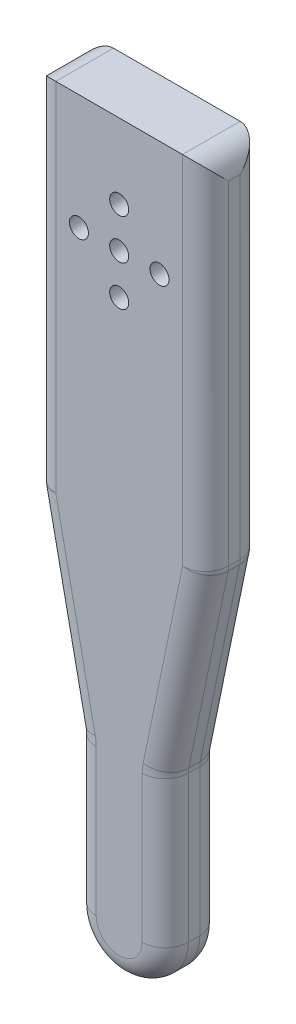
SolidWorks part; units mm, degrees
ref_plane "Front Plane" through (0, 0, 0) normal (0, 0, 1) x (1, 0, 0)
ref_plane "Top Plane" through (0, 0, 0) normal (0, 1, 0) x (1, 0, 0)
ref_plane "Right Plane" through (0, 0, 0) normal (1, 0, 0) x (0, 0, -1)
sketch "Sketch2" plane through (0, 0, 0) normal (0, 0, 1) x (1, 0, 0)
  line L1 (-29.8024, 62.3024) -> (0.1976, 62.3024)
  line L2 (-29.8024, 62.3024) -> (-29.8024, -67.6976)
  line L3 (-29.8024, -67.6976) -> (0.1976, -67.6976)
  line L4 (0.1976, 62.3024) -> (0.1976, -67.6976)
  dimension "D1" = 130
extrude "Boss-Extrude1" add sketch "Sketch2" along normal blind 10
sketch "Sketch3" plane through (0, 0, 10) normal (0, 0, 1) x (1, 0, 0)
  line L0 (-14.8024, 62.3024) -> (-14.8024, 42.3024) construction
  line L1 (0.1976, 62.3024) -> (-29.8024, 62.3024) construction
  line L4 (-29.8024, -67.6976) -> (-21.8024, -67.6976)
  line L5 (-29.8024, -67.6976) -> (-29.8024, 0)
  line L6 (-29.8024, 0) -> (-21.8024, 0)
  line L7 (-21.8024, -67.6976) -> (-21.8024, 0)
  line L9 (0, 0) -> (-7.8024, 0)
  line L10 (0, 0) -> (0, -67.6976)
  line L11 (0, -67.6976) -> (-7.8024, -67.6976)
  line L12 (-7.8024, 0) -> (-7.8024, -67.6976)
  line L13 (-29.8024, -67.6976) -> (0.1976, -67.6976) construction
  circle A0 centre (-14.8024, 42.3024) radius 7 construction
  circle A1 centre (-21.8024, 42.3024) radius 1.65
  circle A2 centre (-14.8024, 49.3024) radius 1.65
  circle A3 centre (-7.8024, 42.3024) radius 1.65
  circle A4 centre (-14.8024, 35.3024) radius 1.65
  circle A5 centre (-14.8024, 42.3024) radius 1.65
  point P5 (-21.8024, 42.3024)
  point P7 (-14.8024, 49.3024)
  point P9 (-7.8024, 42.3024)
  point P11 (-14.8024, 35.3024)
  point P13 (0, 0)
sketch "Sketch6" plane through (0, 0, 10) normal (0, 0, 1) x (1, 0, 0)
  line L1 (-29.8024, -67.6976) -> (-22.8024, -67.6976)
  line L2 (-29.8024, -67.6976) -> (-29.8024, 0)
  line L4 (-22.8024, -67.6976) -> (-22.8024, -33.8488)
  line L11 (0.1976, -67.6976) -> (-6.8024, -67.6976)
  line L12 (0.1976, -67.6976) -> (0.1976, 0)
  line L14 (-6.8024, -67.6976) -> (-6.8024, -33.8488)
  line L15 (-29.8024, 0) -> (-22.8024, -33.8488)
  line L16 (-6.8024, -33.8488) -> (0.1976, 0)
  dimension "D1" = 7
extrude "Cut-Extrude3" cut sketch "Sketch6" against normal through all contours L14 L16 L12 L11 | L4 L15 L2 L1
fillet "Fillet3" 2 edges at (-22.8024, -67.6976, 5) (-6.8024, -67.6976, 5) type full round first side face at (-22.8024, -50.7732, 5) second side face at (-6.8024, -50.7732, 5) middle face at (-14.8024, -67.6976, 5)
fillet "Fillet4" radius 4 20 edges at (-14.8024, -67.6976, 0) (-14.8024, -67.6976, 10) (-6.8024, -46.7732, 0) (-6.8024, -46.7732, 10) (-22.8024, -46.7732, 0) (-22.8024, -46.7732, 10) (0.1976, 31.1512, 10) (0.1976, 62.3024, 5) (0.1976, 31.1512, 0) (0.1976, 0, 5) (-3.3024, -16.9244, 0) (-6.8024, -33.8488, 5) (-3.3024, -16.9244, 10) (-22.8024, -33.8488, 5) (-26.3024, -16.9244, 0) (-26.3024, -16.9244, 10) (-29.8024, 31.1512, 0) (-29.8024, 62.3024, 5) (-29.8024, 31.1512, 10) (-29.8024, 0, 5)
extrude "Cut-Extrude4" cut sketch "Sketch3" against normal through all contours A1 | A4 | A3 | A2 | A5
